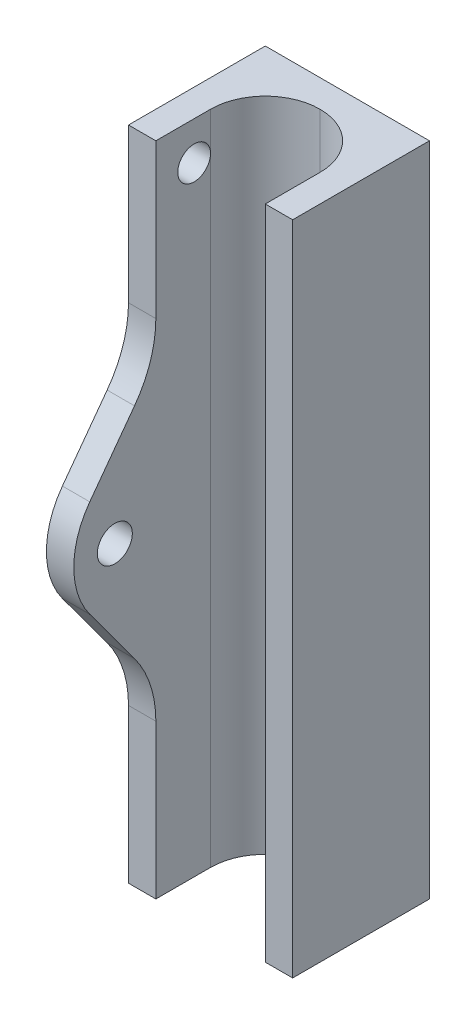
SolidWorks part; units mm, degrees
note: The reader was unsure of these and kept them because the rebuilt part matched: shared geometry of "Sketch1<3>".
ref_plane "Front" through (0, 0, 0) normal (0, 0, 1) x (1, 0, 0)
ref_plane "Top" through (0, 0, 0) normal (0, 1, 0) x (1, 0, 0)
ref_plane "Right" through (0, 0, 0) normal (1, 0, 0) x (0, 0, -1)
sketch "Sketch1" plane through (0, 0, 0) normal (0, 0, 1) x (1, 0, 0)
  line L1 (-9.525, 38.1) -> (9.525, 38.1)
  line L2 (-9.525, 38.1) -> (-9.525, -38.1)
  line L3 (-9.525, -38.1) -> (9.525, -38.1)
  line L4 (9.525, 38.1) -> (9.525, -38.1)
  line L5 (-9.525, 38.1) -> (9.525, -38.1) construction
  line L6 (-9.525, -38.1) -> (9.525, 38.1) construction
  line L7 (6.35, 38.1) -> (-6.35, 38.1)
  line L8 (6.35, 38.1) -> (6.35, -38.1)
  line L9 (6.35, -38.1) -> (-6.35, -38.1)
  line L10 (-6.35, 38.1) -> (-6.35, -38.1)
  line L11 (6.35, 38.1) -> (-6.35, -38.1) construction
  line L12 (6.35, -38.1) -> (-6.35, 38.1) construction
  point P0 (0, 0)
  point P6 (0, 0)
  dimension "D1" = 19.05
  dimension "D2" = 76.2
  dimension "D3" = 3.175
extrude "Boss-Extrude1" add sketch "Sketch1" along normal blind 12.7 contours L10 L1 L2 L3 | L1 L8 L3 L4
extrude "Boss-Extrude2" add sketch "Sketch1<3>" against normal blind 3.175 contours L1 L10 L3 L8 | L1 L8 L3 L4 | L10 L1 L2 L3
sketch "Sketch1<3>" plane through (0, 0, 0) normal (0, 0, 1) x (1, 0, 0) same geometry as "Sketch1"
fillet "Fillet1" radius 6.35 2 edges at (6.35, 0, 0) (-6.35, 0, 0)
sketch "Sketch2" plane through (0, 0, 12.7) normal (0, 0, 1) x (1, 0, 0)
  line L4 (-6.35, -38.1) -> (-6.35, 38.1)
  line L5 (-6.35, 38.1) -> (-9.525, 38.1)
  line L6 (-9.525, 38.1) -> (-9.525, -38.1)
  line L7 (-9.525, -38.1) -> (-6.35, -38.1)
  line L8 (-6.35, -38.1) -> (-6.35, 38.1)
  line L9 (-6.35, 38.1) -> (-9.525, 38.1)
  line L10 (-9.525, 38.1) -> (-9.525, -38.1)
  line L11 (-9.525, -38.1) -> (-6.35, -38.1)
  dimension "D1" = 0
extrude "Boss-Extrude3" add sketch "Sketch2" along normal blind 9.525
sketch "Sketch3" plane through (-6.35, 0, 0) normal (1, 0, 0) x (0, 0, -1)
  line L0 (-22.225, 38.1) -> (-6.35, 38.1) construction
  line L1 (-12.7, 38.1) -> (-12.7, -38.1) construction
  line L2 (-22.225, -38.1) -> (-22.225, 38.1) construction
  line L3 (-22.225, -38.1) -> (-6.35, -38.1) construction
  line L4 (-22.225, 38.1) -> (-6.35, 38.1)
  line L5 (-12.7, -20.2324) -> (-12.7, -38.1)
  line L6 (-22.225, -38.1) -> (-22.225, 38.1)
  line L7 (-22.225, -38.1) -> (-6.35, -38.1)
  line L8 (-20.3688, -5.6493) -> (-15.1749, -12.7)
  line L9 (-17.4625, 0) -> (-12.7, 0) construction
  line L10 (-20.3688, 5.6493) -> (-15.1749, 12.7)
  line L11 (-12.7, 38.1) -> (-12.7, -38.1)
  circle A0 centre (-12.7, 0) radius 9.525
  circle A1 centre (-17.4625, 0) radius 2.032
  arc A2 (-12.7, -20.2324) -> (-15.1749, -12.7) centre (-25.4, -20.2324) ccw
  arc A3 (-12.7, 20.2324) -> (-15.1749, 12.7) centre (-25.4, 20.2324) cw
  dimension "D1" = 4.064
  dimension "D2" = 4.7625
  dimension "D3" = 12.7
  dimension "D4" = 12.7
extrude "Cut-Extrude1" cut sketch "Sketch3" against normal through all both and the other way through all
sketch "Sketch4" plane through (-9.525, 0, 0) normal (-1, 0, 0) x (0, 0, 1)
  line L0 (12.7, 38.1) -> (-3.175, 38.1) construction
  line L1 (12.7, 38.1) -> (12.7, 20.2324) construction
  circle A0 centre (8.255, 33.655) radius 2.032 construction
  circle A1 centre (17.4625, 0) radius 2.032 construction
  circle A2 centre (8.255, 33.655) radius 1.905
  dimension "D1" = 4.445
  dimension "D2" = 4.445
  dimension "D3" = 0.127
extrude "Cut-Extrude2" cut sketch "Sketch4" against normal up to surface (3.175 mm away) up to face at (-6.35, 0, 15.4305)
